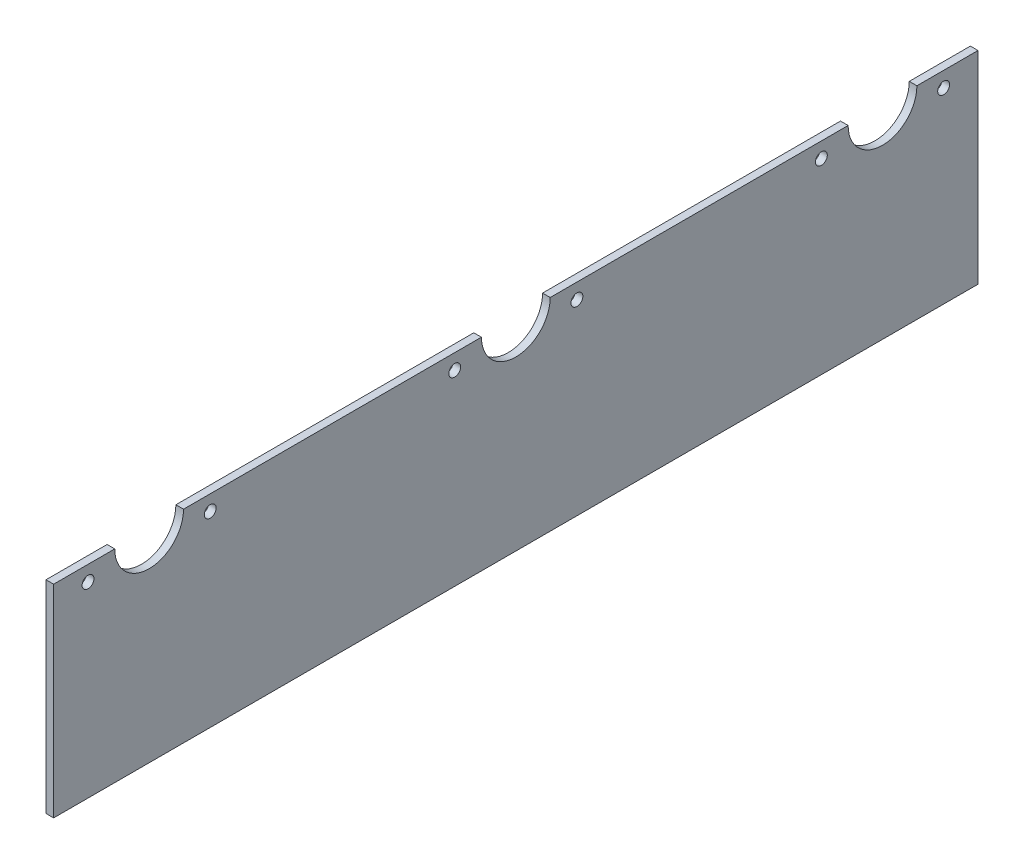
SolidWorks part; units mm, degrees
material "6061 Alloy"
ref_plane "Front Plane" through (0, 0, 0) normal (0, 0, 1) x (1, 0, 0)
ref_plane "Top Plane" through (0, 0, 0) normal (0, 1, 0) x (1, 0, 0)
ref_plane "Right Plane" through (0, 0, 0) normal (1, 0, 0) x (0, 0, -1)
sketch "Sketch1" plane through (0, 0, 0) normal (1, 0, 0) x (0, 0, -1)
  line L0 (192.0875, 0) -> (-192.0875, 0)
  line L1 (-192.0875, 0) -> (-192.0875, 84.1375)
  line L2 (-192.0875, 84.1375) -> (-166.6875, 84.1375)
  line L3 (-138.1125, 84.1375) -> (-14.2875, 84.1375)
  line L4 (14.2875, 84.1375) -> (138.1125, 84.1375)
  line L5 (166.6875, 84.1375) -> (192.0875, 84.1375)
  line L6 (192.0875, 84.1375) -> (192.0875, 0)
  line L7 (-192.0875, 25.4) -> (192.0875, 25.4) construction
  arc A6 (-166.6875, 84.1375) -> (-138.1125, 84.1375) centre (-152.4, 84.1375) ccw
  arc A7 (-14.2875, 84.1375) -> (14.2875, 84.1375) centre (0, 84.1375) ccw
  arc A8 (138.1125, 84.1375) -> (166.6875, 84.1375) centre (152.4, 84.1375) ccw
  point P4 (0, 0)
  dimension "D1" = 25.4
  dimension "D3" = 25.4
  dimension "D5" = 28.575
  dimension "D6" = 44.45
  dimension "D2" = 384.175
  dimension "D4" = 152.4
extrude "Boss-Extrude1" add sketch "Sketch1" along normal blind 3.175
hole_wizard "#10 (0.1935) Diameter Hole1" positions "Sketch2" profile "Sketch3" hole size "#10" standard "ANSI Inch" end condition through all
sketch "Sketch2" plane through (3.175, 0, 0) normal (1, 0, 0) x (0, 0, -1)
  line L0 (-177.8, 77.7875) -> (-127, 77.7875) construction
  line L2 (-25.4, 77.7875) -> (25.4, 77.7875) construction
  line L4 (127, 77.7875) -> (177.8, 77.7875) construction
  line L6 (-166.6875, 84.1375) -> (-192.0875, 84.1375) construction
  line L7 (-152.4, 77.7875) -> (-152.4, 84.1375) construction
  line L9 (0, 84.1375) -> (0, 77.7875) construction
  line L11 (152.4, 84.1375) -> (152.4, 77.7875) construction
  point P0 (-177.8, 77.7875)
  point P2 (-127, 77.7875)
  point P4 (-25.4, 77.7875)
  point P6 (25.4, 77.7875)
  point P8 (127, 77.7875)
  point P10 (177.8, 77.7875)
  dimension "D1" = 50.8
  dimension "D2" = 6.35
sketch "Sketch3" plane through (3.175, 77.7875, 177.8) normal (0, 1, 0) x (0, 0, -1)
  line L0 (0, 0) -> (0, 3.175)
  line L1 (0, 3.175) -> (2.4574, 3.175)
  line L2 (2.4574, 3.175) -> (2.4574, 0)
  line L5 (2.4574, 0) -> (0, 0)
  line L11 (0, -6.35) -> (0, 107.95) construction
  dimension "Thru Hole Dia." = 4.9149
  dimension "Thru Hole Depth" = 3.175
